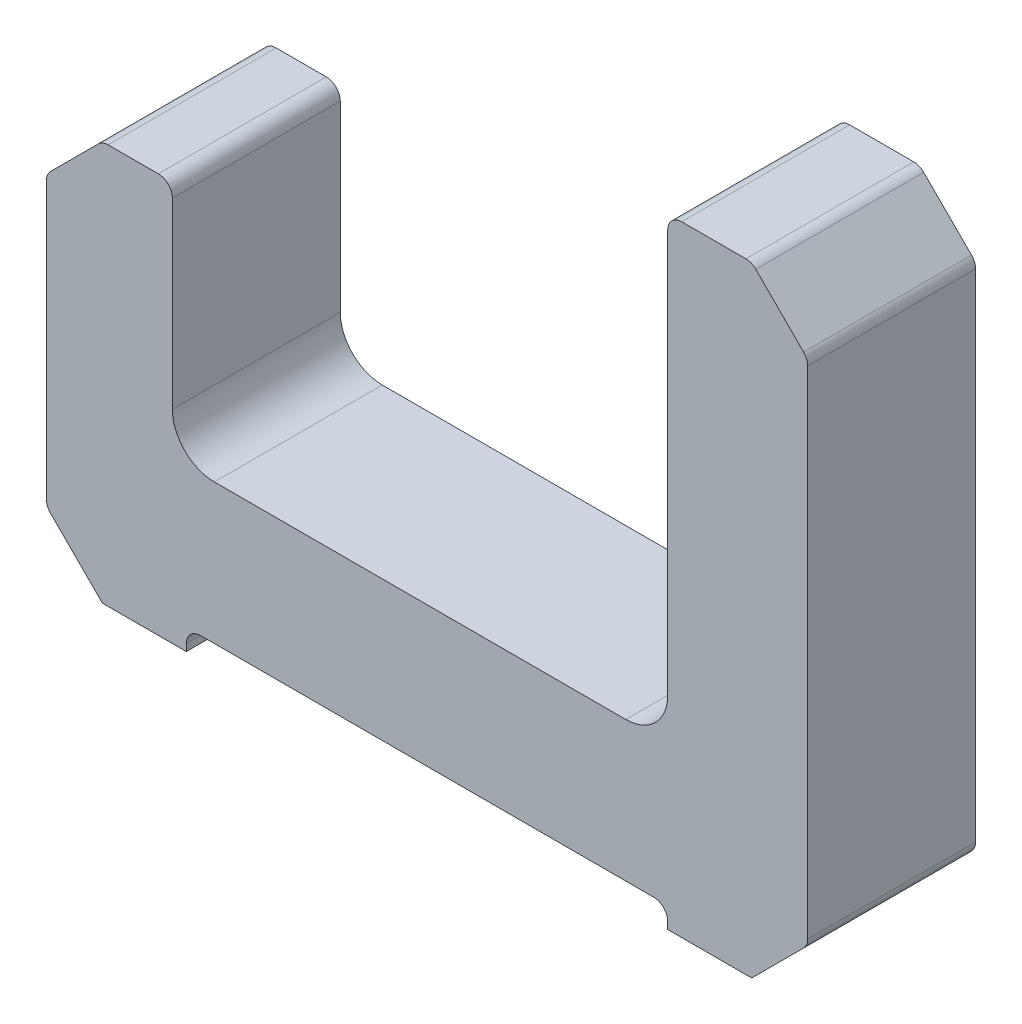
SolidWorks part; units mm, degrees
ref_plane "Front Plane" through (0, 0, 0) normal (0, 0, 1) x (1, 0, 0)
ref_plane "Top Plane" through (0, 0, 0) normal (0, 1, 0) x (1, 0, 0)
ref_plane "Right Plane" through (0, 0, 0) normal (1, 0, 0) x (0, 0, -1)
sketch "Sketch2" plane through (0, 0, 0) normal (0, 0, 1) x (1, 0, 0)
  line L0 (-133.5, 85.3385) -> (-88.5, 85.3385)
  line L1 (-88.5, 85.3385) -> (-88.5, 0)
  line L2 (-88.5, 0) -> (88.5, 0)
  line L3 (88.5, 0) -> (88.5, 164)
  line L4 (88.5, 164) -> (138.5, 164)
  line L5 (138.5, 164) -> (138.5, -57.5)
  line L6 (138.5, -57.5) -> (88.5, -57.5)
  line L7 (88.5, -57.5) -> (88.5, -50)
  line L8 (88.5, -50) -> (-83.5, -50)
  line L9 (-83.5, -50) -> (-83.5, -57.5)
  line L10 (-83.5, -57.5) -> (-133.5, -57.5)
  line L11 (-133.5, -57.5) -> (-133.5, 85.3385)
  line L12 (-33.5, 0) -> (-33.5, 124) construction
  point P10 (-33.5, 0)
  point P14 (88.5, 124)
  point P15 (-33.5, 85.3385)
  dimension "D1" = 124
  dimension "D2" = 122
  dimension "D3" = 55
  dimension "D4" = 40
  dimension "D5" = 50
  dimension "D6" = 50
  dimension "D7" = 7.5
  dimension "D8" = 45
extrude "Boss-Extrude1" add sketch "Sketch2" along normal blind 30 and the other way blind 30
chamfer "Chamfer1" distance 20 angle 45 4 edges at (-133.5, -57.5, 0) (138.5, -57.5, 0) (138.5, 164, 0) (-133.5, 85.3385, 0)
fillet "Fillet1" radius 15 2 edges at (88.5, 0, 0) (-88.5, 0, 0)
fillet "Fillet2" radius 5 10 edges at (138.5, -37.5, 0) (88.5, -50, 0) (-83.5, -50, 0) (-133.5, -37.5, 0) (-133.5, 65.3385, 0) (-113.5, 85.3385, 0) (-88.5, 85.3385, 0) (138.5, 144, 0) (118.5, 164, 0) (88.5, 164, 0)
equation "\"dX\"= 122mm"
equation "\"dY\"= 124mm"
equation "\"hmotor\"= 50mm"
equation "\"D1@Sketch2\"=\"dY\""
equation "\"D2@Sketch2\"=\"dX\""
equation "\"D5@Sketch2\"=\"hmotor\""
equation "\"D6@Sketch2\"=\"hmotor\""
